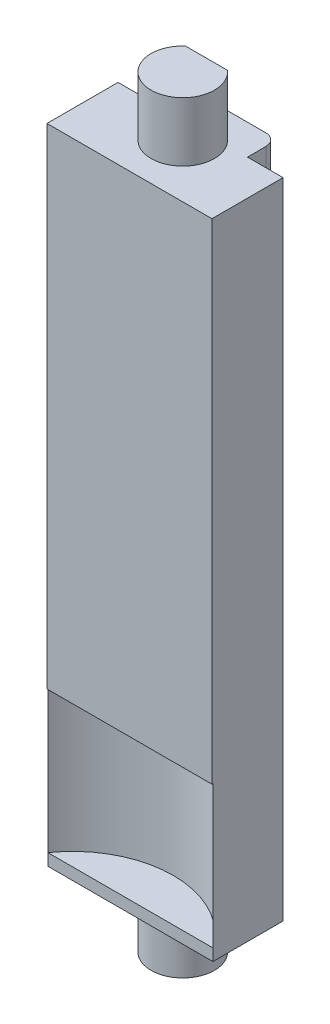
SolidWorks part; units mm, degrees
ref_plane "Front Plane" through (0, 0, 0) normal (0, 0, 1) x (1, 0, 0)
ref_plane "Top Plane" through (0, 0, 0) normal (0, 1, 0) x (1, 0, 0)
ref_plane "Right Plane" through (0, 0, 0) normal (1, 0, 0) x (0, 0, -1)
sketch "Sketch1" plane through (0, 0, 0) normal (0, 1, 0) x (1, 0, 0)
  line L0 (0, -2.55) -> (-3, -2.55)
  line L1 (0, 0) -> (7.92, 0)
  line L2 (0, 0) -> (0, -2.55)
  line L3 (0, -2.55) -> (7.92, -2.55)
  line L4 (7.92, 0) -> (7.92, -2.55)
  line L5 (-3, -8.55) -> (10.92, -8.55)
  line L6 (-3, -2.55) -> (-3, -8.55)
  line L7 (10.92, -8.55) -> (10.92, -2.55)
  line L8 (10.92, -2.55) -> (7.92, -2.55)
  point P5 (3.96, -2.55)
  dimension "D1" = 7.92
  dimension "D2" = 2.55
  dimension "D3" = 6
  dimension "D4" = 3
extrude "Boss-Extrude1" add sketch "Sketch1" along normal blind 54.32 contours L4 L1 L2 L3 | L5 L3 | L3 L0 L6 | L7 L8 L3 | L3 | L5 region at (3.96, 0, 5.55) region at (3.96, 0, 1.275)
fillet "Fillet1" radius 1 2 edges at (7.92, 27.16, 0) (0, 27.16, 0)
sketch "Sketch2" plane through (0, 54.32, 0) normal (0, 1, 0) x (1, 0, 0)
  line L1 (10.92, -2.55) -> (7.92, -2.55) construction
  line L3 (1, 0) -> (6.92, 0) construction
  line L4 (2.1836, -2.05) -> (5.7364, -2.05)
  circle A0 centre (3.96, -4.05) radius 2.675
  point P1 (3.96, -4.05)
  point P4 (3.96, 0)
  point P5 (3.96, -3.55)
  dimension "D1" = 5.35
  dimension "D2" = 1.5
  dimension "D3" = 2
extrude "Boss-Extrude2" add sketch "Sketch2" along normal blind 5 contours L4 A0 region at (3.96, 54.32, 4.2294)
ref_plane "Plane1" through (0, 27.16, 0) normal (0, 1, 0) x (1, 0, 0)
mirror "Mirror1" about plane through (0, 27.16, 0) normal (0, 1, 0) of "Boss-Extrude2"
ref_plane "Plane2" through (0, 0, 0) normal (0, -1, 0) x (-1, 0, 0)
sketch "Sketch3" plane through (0, 0, 0) normal (0, -1, 0) x (1, 0, 0)
  line L0 (1, 0) -> (6.92, 0) construction
  circle A3 centre (3.96, 13.3485) radius 8.5
  point P2 (3.96, 0)
  dimension "D1" = 17
extrude "Cut-Extrude1" cut sketch "Sketch3" against normal blind 13
sketch "Sketch4" plane through (0, 0, 0) normal (0, 1, 0) x (1, 0, 0)
  line L0 (-3, -8.4691) -> (10.92, -8.4691)
  arc A0 (6.3757, -5.199) -> (1.5443, -5.199) centre (3.96, -13.3485) ccw construction
  arc A2 (6.3757, -5.199) -> (1.5443, -5.199) centre (3.96, -13.3485) ccw
  arc A3 (1.5443, -5.199) -> (-3, -8.4691) centre (3.96, -13.3485) ccw construction
  arc A4 (10.92, -8.4691) -> (6.3757, -5.199) centre (3.96, -13.3485) ccw construction
  arc A5 (1.5443, -5.199) -> (-3, -8.4691) centre (3.96, -13.3485) ccw
  arc A6 (10.92, -8.4691) -> (6.3757, -5.199) centre (3.96, -13.3485) ccw
extrude "Boss-Extrude3" add sketch "Sketch4" along normal blind 1
